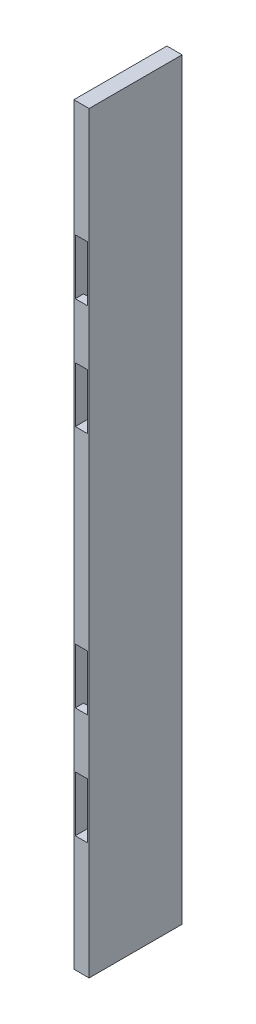
SolidWorks part; units mm, degrees
ref_plane "Top" through (0, 0, 0) normal (0, 0, 1) x (1, 0, 0)
ref_plane "Front" through (0, 0, 0) normal (0, 1, 0) x (1, 0, 0)
ref_plane "Right" through (0, 0, 0) normal (1, 0, 0) x (0, 0, -1)
sketch "Profile Sketch" plane through (0.0456, 0, -0.0242) normal (0, 1, 0) x (-1, 0, 0)
  line L0 (2.5456, -16.7758) -> (2.5456, 0.0242)
  line L1 (2.5456, 0.0242) -> (0.0456, 0.0242)
  line L2 (0.0456, 0.0242) -> (0.0456, -16.7758)
  line L3 (0.0456, -16.7758) -> (2.5456, -16.7758)
  line L12 (2.2956, 0.0242) -> (2.2956, -16.7758) construction
  dimension "D1" = 16.8
  dimension "D3" = 2.25
  dimension "Cover Thickness" = 0.25
extrude "Profile Extrude" add sketch "Profile Sketch" along normal blind 136
ref_plane "Mid Plane" through (0, 68, 0) normal (0, -1, 0) x (-1, 0, 0)
ref_plane "Right Cut Out Location" through (0, 36, 0) normal (0, -1, 0) x (-1, 0, 0)
ref_plane "Left Cut Out Location" through (0, 100, 0) normal (0, -1, 0) x (-1, 0, 0)
sketch "Cover Latch Cut Out Sketch" plane through (-2.5, 0, 0) normal (-1, 0, 0) x (0, 0, 1)
  line L4 (-16.8, 43) -> (-16.8, 29)
  line L5 (0, 31) -> (-1.5, 31)
  line L10 (0, 41) -> (0, 31) construction
  line L11 (0, 136) -> (0, 0) construction
  line L12 (-1.5, 31) -> (-2.1583, 36)
  line L13 (-2.1583, 36) -> (-1.5, 41)
  line L14 (-1.5, 41) -> (0, 41)
  line L15 (-2.1583, 36) -> (0, 36) construction
  line L16 (0, 41) -> (0, 51)
  line L17 (0, 51) -> (-8.1583, 51)
  line L18 (0, 31) -> (0, 21)
  line L21 (0, 21) -> (-8.1583, 21)
  line L22 (-8.1583, 51) -> (-8.1583, 43)
  line L23 (-8.1583, 43) -> (-16.8, 43)
  line L24 (-8.1583, 21) -> (-8.1583, 29)
  line L25 (-8.1583, 29) -> (-16.8, 29)
  line L27 (-16.8, 136) -> (-16.8, 0) construction
  point P3 (0, 68)
  dimension "D1" = 1.5
  dimension "D2" = 10
  dimension "D3" = 10
  dimension "D4" = 7.5
  dimension "D5" = 6
  dimension "Latch Position" = 32
extrude "Cover Latch Cut Out" cut sketch "Cover Latch Cut Out Sketch" against normal blind 2.25
mirror "Cover Latch Cut Out Mirror" about plane through (0, 68, 0) normal (0, -1, 0) of "Cover Latch Cut Out"
sketch "Side Sketch" plane through (0, 0, 0) normal (0, 1, 0) x (1, 0, 0)
  line L7 (-2.75, 16.8) -> (-2.5, 16.8)
  line L8 (-2.75, 16.8) -> (-2.75, 0)
  line L9 (-2.75, 0) -> (-2.5, 0)
  line L10 (-2.5, 16.8) -> (-2.5, 0)
  dimension "Cover Thickness" = 0.25
extrude "Side Extrude" add sketch "Side Sketch" along normal through all
